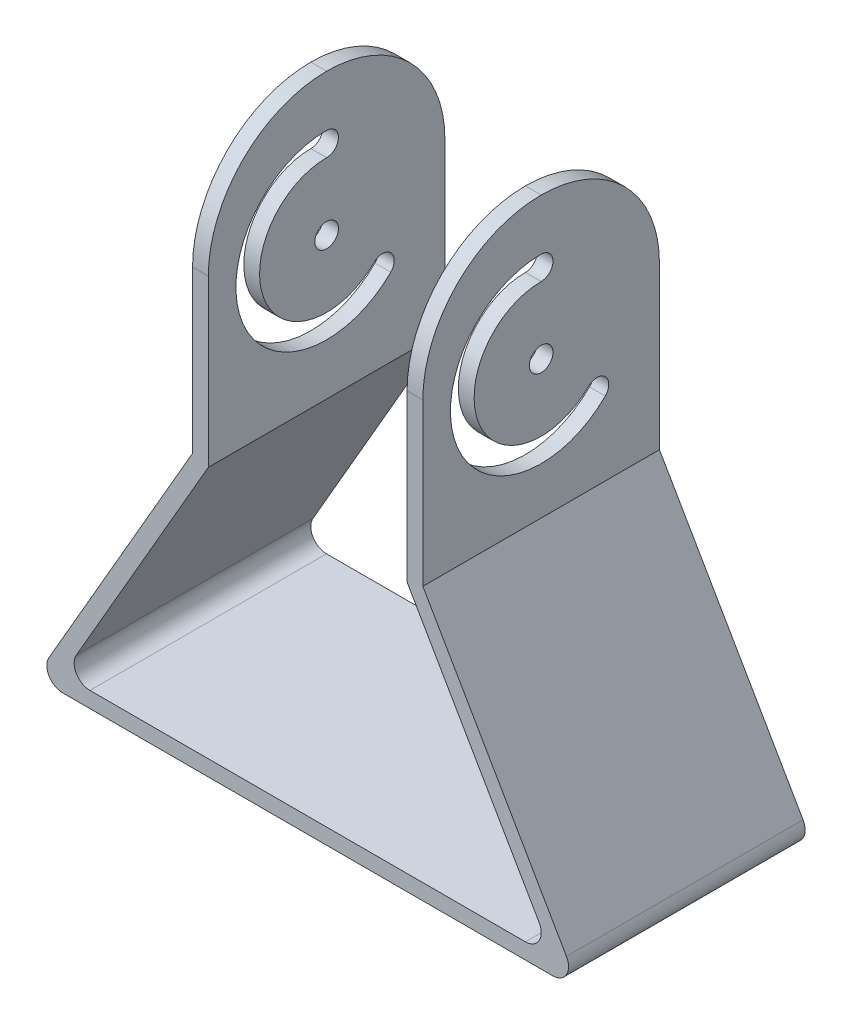
SolidWorks part; units mm, degrees
ref_plane "Alzado" through (0, 0, 0) normal (0, 0, 1) x (1, 0, 0)
ref_plane "Planta" through (0, 0, 0) normal (0, 1, 0) x (1, 0, 0)
ref_plane "Vista lateral" through (0, 0, 0) normal (1, 0, 0) x (0, 0, -1)
sketch "Croquis1" plane through (0, 0, 0) normal (0, 0, 1) x (1, 0, 0)
  line L0 (-245.6966, 350) -> (-245.6966, 172.6795)
  line L2 (-99.6966, 172.6795) -> (-99.6966, 350)
  line L3 (-99.6966, 350) -> (-109.6966, 350)
  line L7 (-235.6966, 350) -> (-245.6966, 350)
  line L8 (-245.6966, 172.6795) -> (-345.3931, 0)
  line L9 (-345.3931, 0) -> (0, 0)
  line L10 (-99.6966, 172.6795) -> (0, 0)
  line L12 (-235.6966, 170) -> (-328.0726, 10)
  line L13 (-328.0726, 10) -> (-17.3205, 10)
  line L14 (-109.6966, 170) -> (-17.3205, 10)
  line L16 (-235.6966, 350) -> (-235.6966, 170)
  line L17 (-109.6966, 350) -> (-109.6966, 170)
  point P3 (-1.1497, 1.9913)
  point P6 (-18.0412, 11.2482)
  point P7 (0, 0)
  point P17 (0, 0)
  dimension "D2" = 10
  dimension "D3" = 10
  dimension "D4" = 10
  dimension "D5" = 10
  dimension "D6" = 60
  dimension "D7" = 350
  dimension "D8" = 60
  dimension "D9" = 126
  dimension "D10" = 10
  dimension "D11" = 180
extrude "Saliente-Extruir1" add sketch "Croquis1" along normal blind 150
sketch "Croquis2" plane through (-245.6966, 0, 0) normal (-1, 0, 0) x (0, 0, 1)
  line L1 (0, 350) -> (0, 172.6795) construction
  line L2 (150, 350) -> (0, 350) construction
  line L3 (75, 310) -> (75, 260) construction
  line L4 (75, 260) -> (125, 260) construction
  line L5 (75, 260) -> (39.6447, 224.6447) construction
  circle A0 centre (75, 260) radius 7.5
  arc A1 (39.6447, 224.6447) -> (75, 310) centre (75, 260) ccw construction
  arc A6 (34.3414, 219.3414) -> (75, 317.5) centre (75, 260) ccw
  arc A7 (44.948, 229.948) -> (75, 302.5) centre (75, 260) ccw
  arc A8 (44.948, 229.948) -> (34.3414, 219.3414) centre (39.6447, 224.6447) ccw
  arc A9 (75, 317.5) -> (75, 302.5) centre (75, 310) ccw
  point P8 (121.194, 240.8658)
  dimension "D3" = 15
  dimension "D4" = 7.5
  dimension "D7" = 45
  dimension "D1" = 90
  dimension "D2" = 75
  dimension "D5" = 50
  dimension "D6" = 90
extrude "Cortar-Extruir1" cut sketch "Croquis2" against normal blind 146
fillet "Redondeo1" radius 75 4 edges at (-104.6966, 350, 0) (-104.6966, 350, 150) (-240.6966, 350, 150) (-240.6966, 350, 0)
fillet "Redondeo2" radius 10 4 edges at (-17.3205, 10, 75) (0, 0, 75) (-328.0726, 10, 75) (-345.3931, 0, 75)
